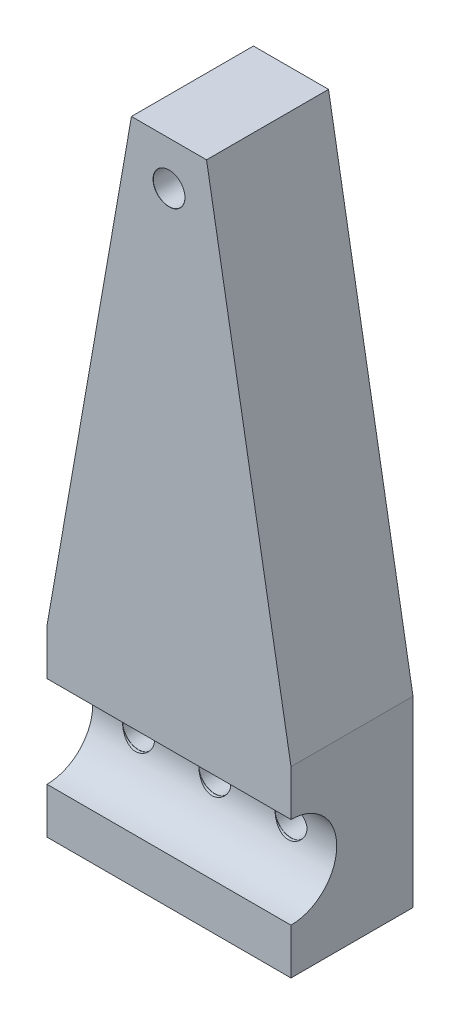
SolidWorks part; units mm, degrees
ref_plane "Front Plane" through (0, 0, 0) normal (0, 0, 1) x (1, 0, 0)
ref_plane "Top Plane" through (0, 0, 0) normal (0, 1, 0) x (1, 0, 0)
ref_plane "Right Plane" through (0, 0, 0) normal (1, 0, 0) x (0, 0, -1)
sketch "Sketch1" plane through (0, 0, 0) normal (0, 0, 1) x (1, 0, 0)
  line L0 (-25.4, 19.05) -> (-7.8164, 119.6762)
  line L1 (25.4, -19.05) -> (-25.4, -19.05)
  line L2 (25.4, -19.05) -> (25.4, 19.05)
  line L3 (25.4, 19.05) -> (-25.4, 19.05)
  line L4 (-25.4, -19.05) -> (-25.4, 19.05)
  line L5 (25.4, -19.05) -> (-25.4, 19.05) construction
  line L6 (25.4, 19.05) -> (-25.4, -19.05) construction
  line L7 (-7.8164, 119.6762) -> (7.8164, 119.6762)
  line L8 (7.8164, 119.6762) -> (25.4, 19.05)
  line L9 (-15.875, 0) -> (15.875, 0) construction
  line L10 (0, 119.6762) -> (0, 110.6189) construction
  point P0 (0, 0)
  point P8 (0, 119.6762)
  point P9 (0, 0)
  dimension "D1" = 50.8
  dimension "D2" = 38.1
  dimension "D4" = 31.75
extrude "Boss-Extrude1" add sketch "Sketch1" along normal blind 25.4 contours L8 L7 L0 L3 | L4 L1 L2 L3 region at (0, 60.4851, 0) region at (0, 0, 0)
sketch "Sketch2" plane through (0, 0, 25.4) normal (0, 0, 1) x (1, 0, 0)
  line L0 (-25.4, 0) -> (25.4, 0)
  line L1 (-25.4, -19.05) -> (-25.4, 19.05) construction
  line L2 (25.4, -19.05) -> (25.4, 19.05) construction
sweep "Cut-Sweep1" cut path "Sketch2" circular profile diameter 19.05 parameters "D3"=19.05
hole_wizard "M6 Clearance Hole1" positions "3DSketch1" profile "Sketch9" hole size "M6" standard "ANSI Metric" end condition through all
sketch3d "3DSketch1"
  point P0 (0, 0, 15.875)
  point P4 (-15.875, 0, 15.875)
  point P6 (15.875, 0, 15.875)
  point P8 (0, 110.6189, 25.4)
sketch "Sketch9" plane through (0, 0, 15.875) normal (1, 0, 0) x (0, -1, 0)
  line L0 (0, 0) -> (0, 15.875)
  line L1 (0, 15.875) -> (3.3, 15.875)
  line L2 (3.3, 15.875) -> (3.3, 0.025)
  line L3 (3.3, 0.025) -> (3.325, 0)
  line L5 (3.325, 0) -> (0, 0)
  line L6 (-3.3, 0.025) -> (-3.325, 0) construction
  line L11 (0, -6.35) -> (0, 107.95) construction
  dimension "Thru Hole Dia." = 6.6
  dimension "Thru Hole Depth" = 15.875
  dimension "Near C'Sink Dia." = 6.65
  dimension "Near C'Sink Angle" = 90
equation "\"Rover_Length\"= 25in"
equation "\"Rover_Width\"= 18in"
equation "\"Rover_Height\"= 12in"
equation "\"Chassis_Wheelbase\"= 28in"
equation "\"Chassis_WheelDiam\"= 171mm"
equation "\"Chassis_ArmDiamWidth\"= 0.75in"
equation "\"Chassis_ArmAngle\"= 135deg"
equation "\"Chassis_ArmHeight\"= 8in"
equation "\"Chassis_HubMountOD\"= 3in"
equation "\"Chassis_WheelBoltHole\"= 36mm"
equation "\"Chassis_WheelBoltNum\"= 4"
equation "\"Chassis_DiffBarLength\"= 12in"
equation "\"Chassis_DiffBarWidth\"= 1in"
equation "\"Chassis_DiffBarHeight\"= 0.5in"
equation "\"Chassis_DiffLinkage_Length\"= 2.5in"
equation "\"Chassis_MountBracketThickness\"= 0.125in"
equation "\"Chassis_MountBracketWidth\"= 3in"
equation "\"Chassis_MountBacketOverlap\"= 0.5in"
equation "\"Chassis_ArmShaftDiam\"= 0.75in"
equation "\"Chassis_ArmHoleSpacing\"= 1.25in"
equation "\"D4@Sketch1\"=\"Chassis_ArmHoleSpacing\""
